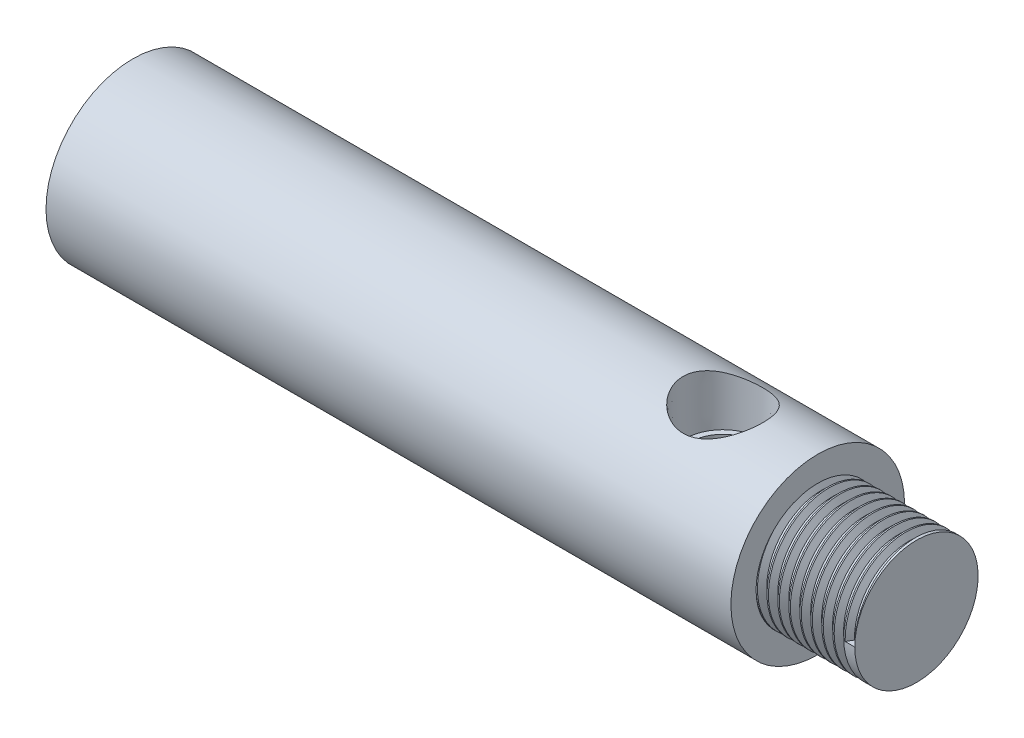
SolidWorks part; units mm, degrees
ref_plane "Front Plane" through (0, 0, 0) normal (0, 0, 1) x (1, 0, 0)
ref_plane "Top Plane" through (0, 0, 0) normal (0, 1, 0) x (1, 0, 0)
ref_plane "Right Plane" through (0, 0, 0) normal (1, 0, 0) x (0, 0, -1)
sketch "Sketch1" plane through (0, 0, 0) normal (1, 0, 0) x (0, 0, -1)
  circle A0 centre (0, 0) radius 11.176
  dimension "D1" = 22.352
extrude "Boss-Extrude1" add sketch "Sketch1" along normal blind 88.138
sketch "Sketch2" plane through (88.138, 0, 0) normal (1, 0, 0) x (0, 0, -1)
  circle A0 centre (0, 0) radius 7.9375
  dimension "D1" = 15.875
extrude "Boss-Extrude2" add sketch "Sketch2" along normal blind 12.7
thread "Thread1" pitch 1.4111 method cut profile "Thread Profile1" start angle 0, offset 0, length 12.7, pitch 1.4111, diameter 15.875
ref_plane "Plane1" through (100.838, 0, 7.9375) normal (0, -1, 0) x (0, 0, 1)
sketch "Thread Profile1" plane through (100.838, 0, 7.9375) normal (0, -1, 0) x (0, 0, 1)
  line L0 (0, 0) -> (0, 1.4111) construction
  line L11 (0, 0) -> (0, 1.2347)
  line L12 (0, 1.2347) -> (-0.7638, 0.7937)
  line L13 (-0.7638, 0.7937) -> (-0.7638, 0.441)
  line L15 (-0.7638, 0.441) -> (0, 0)
  line L17 (-0.7638, 0.6174) -> (0, 0.6174) construction
  point P2 (0, 0)
  dimension "Pitch" = 1.4111
  dimension "Profile_Angle" = 60
  dimension "Profile_Land" = 0.3528
  dimension "Profile_Height" = 0.7638
ref_plane "Plane2" through (0, 11.176, 0) normal (0, 1, 0) x (1, 0, 0)
hole_wizard "1/8 NPT Tapped Hole1" positions "Sketch6" profile "Sketch7" size "1/8" standard "ANSI Inch"
sketch "Sketch6" plane through (0, 11.176, 0) normal (0, 1, 0) x (1, 0, 0)
  line L0 (88.138, -11.176) -> (88.138, 11.176) construction
  point P0 (75.946, 0)
  dimension "D1" = 12.192
sketch "Sketch7" plane through (75.946, 11.176, 0) normal (1, 0, 0) x (0, 0, 1)
  line L0 (0, 0) -> (0, 14.2175)
  line L1 (4.2164, 11.684) -> (0, 14.2175)
  line L2 (-4.2164, 11.684) -> (0, 14.2175) construction
  line L3 (4.2164, 11.684) -> (4.2164, 6.858)
  line L4 (4.2164, 6.858) -> (4.9362, 6.858)
  line L5 (4.9362, 6.858) -> (5.1415, 0)
  line L6 (-4.9362, 6.858) -> (-5.1415, 0) construction
  line L7 (5.1415, 0) -> (0, 0)
  line L8 (0, -6.35) -> (0, 107.95) construction
  line L11 (-4.2164, 6.858) -> (-4.9362, 6.858) construction
  dimension "Tap Drill Dia." = 8.4328
  dimension "Tap Drill Depth" = 11.684
  dimension "Thread Dia." = 10.283
  dimension "Thread Angle" = 3.43
  dimension "Thread Depth" = 6.858
  dimension "Drill Angle" = 118
hole_wizard "1/8 NPT Tapped Hole2" positions "Sketch8" profile "Sketch9" size "1/8" standard "ANSI Inch"
sketch "Sketch8" plane through (0, 0, 0) normal (-1, 0, 0) x (0, 0, 1)
  point P0 (0, 0)
sketch "Sketch9" plane through (0, 0, 0) normal (0, 1, 0) x (0, 0, 1)
  line L0 (0, 0) -> (0, 14.2175)
  line L1 (4.2164, 11.684) -> (0, 14.2175)
  line L2 (-4.2164, 11.684) -> (0, 14.2175) construction
  line L3 (4.2164, 11.684) -> (4.2164, 6.858)
  line L4 (4.2164, 6.858) -> (4.9362, 6.858)
  line L5 (4.9362, 6.858) -> (5.1415, 0)
  line L6 (-4.9362, 6.858) -> (-5.1415, 0) construction
  line L7 (5.1415, 0) -> (0, 0)
  line L8 (0, -6.35) -> (0, 107.95) construction
  line L11 (-4.2164, 6.858) -> (-4.9362, 6.858) construction
  dimension "Tap Drill Dia." = 8.4328
  dimension "Tap Drill Depth" = 11.684
  dimension "Thread Dia." = 10.283
  dimension "Thread Angle" = 3.43
  dimension "Thread Depth" = 6.858
  dimension "Drill Angle" = 118
